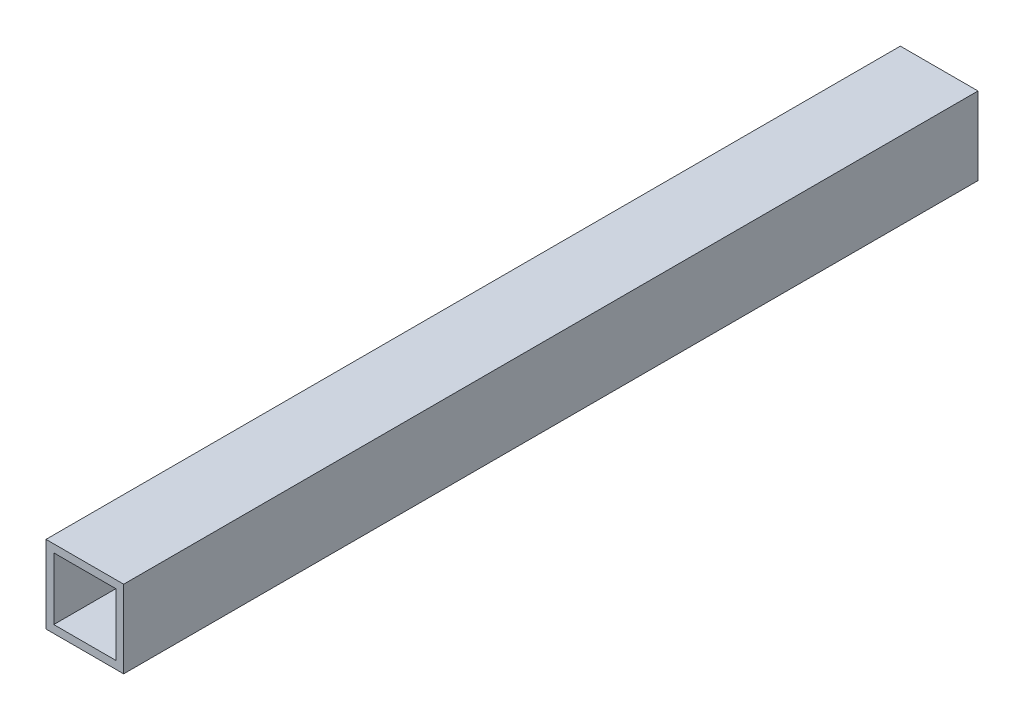
SolidWorks part; units mm, degrees
ref_plane "Płaszczyzna przednia" through (0, 0, 0) normal (0, 0, 1) x (1, 0, 0)
ref_plane "Płaszczyzna górna" through (0, 0, 0) normal (0, 1, 0) x (1, 0, 0)
ref_plane "Płaszczyzna prawa" through (0, 0, 0) normal (1, 0, 0) x (0, 0, -1)
sketch "Szkic1" plane through (0, 0, 0) normal (0, 0, 1) x (1, 0, 0)
  line L1 (-10, 10) -> (10, 10)
  line L2 (-10, 10) -> (-10, -10)
  line L3 (-10, -10) -> (10, -10)
  line L4 (10, 10) -> (10, -10)
  line L5 (-10, 10) -> (10, -10) construction
  line L6 (-10, -10) -> (10, 10) construction
  line L7 (-8, -8) -> (8, -8)
  line L8 (-8, -8) -> (-8, 8)
  line L9 (-8, 8) -> (8, 8)
  line L10 (8, -8) -> (8, 8)
  line L11 (-8, -8) -> (8, 8) construction
  line L12 (-8, 8) -> (8, -8) construction
  point P0 (0, 0)
  point P5 (0, 0)
  dimension "D1" = 20
  dimension "D2" = 16
extrude "Dodanie-wyciągnięcie1" add sketch "Szkic1" along normal blind 220
